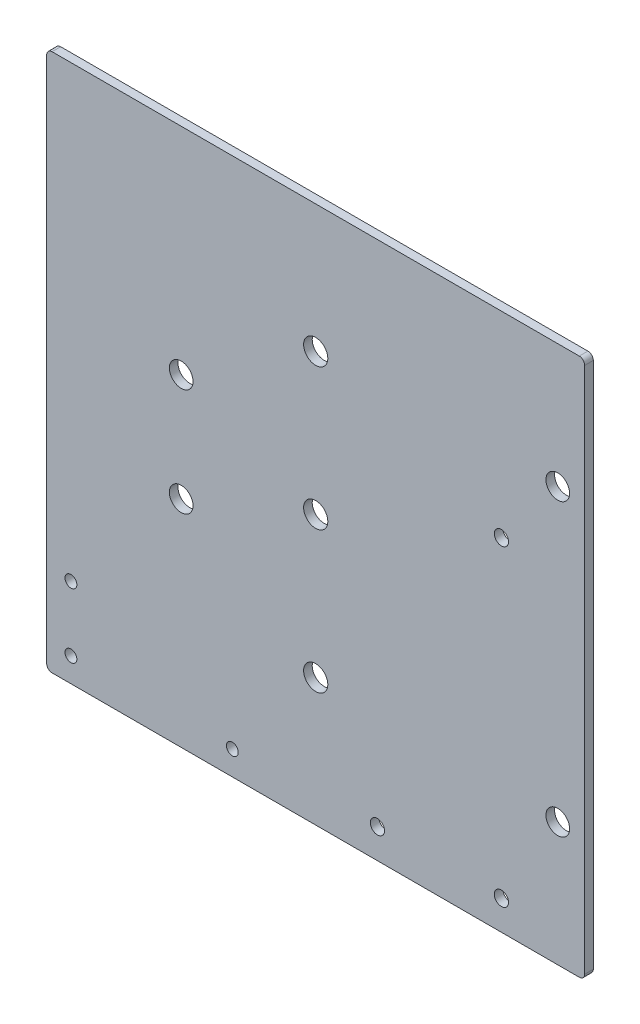
SolidWorks part; units mm, degrees
material "FR4_stuffedProtoboard"
ref_plane "Front Plane" through (0, 0, 0) normal (0, 0, 1) x (1, 0, 0)
ref_plane "Top Plane" through (0, 0, 0) normal (0, 1, 0) x (1, 0, 0)
ref_plane "Right Plane" through (0, 0, 0) normal (1, 0, 0) x (0, 0, -1)
sketch "Sketch1" plane through (0, 0, 0) normal (0, 0, 1) x (1, 0, 0)
  line L1 (-50, -50) -> (50, -50)
  line L2 (-50, -50) -> (-50, 50)
  line L3 (-50, 50) -> (50, 50)
  line L4 (50, -50) -> (50, 50)
  line L5 (-50, -50) -> (50, 50) construction
  line L6 (-50, 50) -> (50, -50) construction
  dimension "D1" = 100
extrude "Boss-Extrude1" add sketch "Sketch1" along normal blind 1.6
sketch "Sketch2" [suppressed] plane through (0, 0, 1.6) normal (0, 0, 1) x (1, 0, 0)
  circle A0 centre (0, 0) radius 50
  line M2 (50, -50) -> (50, 50)
  line M3 (50, 50) -> (-50, 50)
  line M4 (-50, 50) -> (-50, -50)
  line M5 (-50, -50) -> (50, -50)
  dimension "D1" = 100
extrude "Cut-Extrude1" [suppressed] cut sketch "Sketch2" against normal blind 1.6 contours A0 M3 M4 | A0 M4 M5 | A0 M5 M2 | A0 M2 M3
sketch "Sketch3" plane through (0, 0, 0) normal (0, 0, -1) x (-1, 0, 0)
  circle A0 centre (0, -26.25) radius 2.2479 construction
  circle A2 centre (0, -26.25) radius 2.2479
  circle A3 centre (0, 0) radius 2.2479
  circle A4 centre (-34.525, -44.525) radius 1.325 construction
  circle A6 centre (-34.525, -44.525) radius 1.325
  circle A8 centre (0, 26.25) radius 2.2479 construction
  circle A9 centre (0, 26.25) radius 2.2479
  circle A10 centre (-45, -27) radius 2.2 construction
  circle A11 centre (-45, -27) radius 2.2
  circle A12 centre (-45, 27) radius 2.2 construction
  circle A13 centre (-45, 27) radius 2.2
  circle A14 centre (-34.525, 13.525) radius 1.325 construction
  circle A15 centre (-34.525, 13.525) radius 1.325
  circle A16 centre (15.5, -45.5) radius 1.1 construction
  circle A17 centre (15.5, -45.5) radius 1.1
  circle A18 centre (45.5, -45.5) radius 1.1 construction
  circle A19 centre (45.5, -45.5) radius 1.1
  circle A20 centre (45.5, -33.5) radius 1.1 construction
  circle A21 centre (45.5, -33.5) radius 1.1
  circle A22 centre (-11.475, -44.525) radius 1.325 construction
  circle A23 centre (-11.475, -44.525) radius 1.325
  circle A24 centre (25, -10) radius 2.2 construction
  circle A25 centre (25, -10) radius 2.2
  circle A26 centre (25, 10) radius 2.2 construction
  circle A27 centre (25, 10) radius 2.2
  dimension "D1" = 4.4958
extrude "Cut-Extrude2" cut sketch "Sketch3" against normal up to surface (1.6 mm away) up to face at (0, 0, 1.6)
sketch "Sketch4" plane through (0, 0, 1.6) normal (0, 0, 1) x (1, 0, 0)
  line L0 (38, -44.25) -> (38, -18.925) construction
  line L5 (38, -44.25) -> (38, -18.925)
  line L6 (11.75, -48) -> (34.25, -48) construction
  line L7 (11.75, -48) -> (34.25, -48)
  line L8 (8, -44.25) -> (8, 13.25) construction
  line L9 (8, -44.25) -> (8, 13.25)
  line L11 (33, -3) -> (33, -48) construction
  line L13 (34.25, 17) -> (11.75, 17)
  line L14 (38, 13.25) -> (38, -18.925)
  line L15 (-48, -48) -> (-13, -48) construction
  line L16 (-48, -48) -> (-13, -48)
  line L17 (-48, -31) -> (-48, -48) construction
  line L18 (-48, -31) -> (-48, -48)
  line L19 (-13, -40.5) -> (-13, -32.5) construction
  line L20 (-13, -40.5) -> (-13, -32.5)
  line L21 (-13, -48) -> (-13, -40.5) construction
  line L22 (-13, -48) -> (-13, -40.5)
  line L23 (-13, -32.5) -> (-13, -31) construction
  line L24 (-13, -32.5) -> (-13, -31)
  line L25 (-13, -31) -> (-48, -31) construction
  line L26 (-13, -31) -> (-48, -31)
  line L27 (-20, -34) -> (-20, -48) construction
  arc A0 (34.25, -48) -> (38, -44.25) centre (34.25, -44.25) ccw construction
  arc A1 (34.25, -48) -> (38, -44.25) centre (34.25, -44.25) ccw
  arc A2 (8, -44.25) -> (11.75, -48) centre (11.75, -44.25) ccw construction
  arc A3 (8, -44.25) -> (11.75, -48) centre (11.75, -44.25) ccw
  arc A4 (11.75, 17) -> (8, 13.25) centre (11.75, 13.25) ccw construction
  arc A5 (11.75, 17) -> (8, 13.25) centre (11.75, 13.25) ccw
  arc A6 (38, 13.25) -> (34.25, 17) centre (34.25, 13.25) ccw construction
  arc A7 (38, 13.25) -> (34.25, 17) centre (34.25, 13.25) ccw
  text T0 "Raspberry Pi Zero W" font "Century Gothic" height 2
  text T1 "Atheros" font "Century Gothic" height 2
  dimension "D1" = 5
  dimension "D2" = 20
  dimension "D3" = 3
  dimension "D4" = 7
fillet "Fillet1" radius 1 4 edges at (-50, -50, 0.8) (-50, 50, 0.8) (50, -50, 0.8) (50, 50, 0.8)
